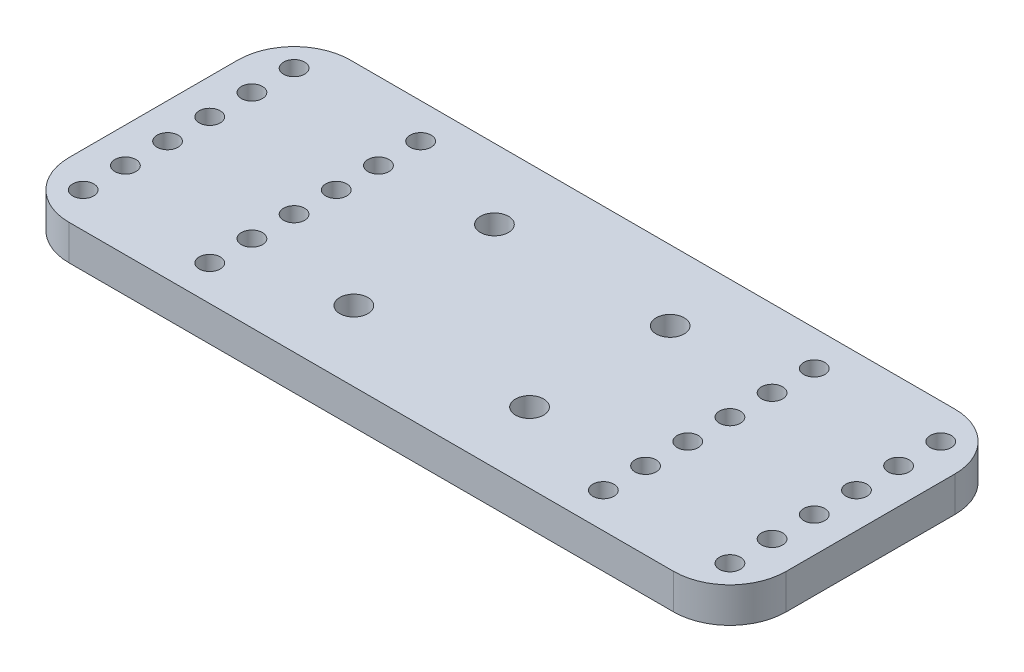
SolidWorks part; units mm, degrees
ref_plane "前视基准面" through (0, 0, 0) normal (0, 0, 1) x (1, 0, 0)
ref_plane "上视基准面" through (0, 0, 0) normal (0, 1, 0) x (1, 0, 0)
ref_plane "右视基准面" through (0, 0, 0) normal (1, 0, 0) x (0, 0, -1)
sketch "草图1" plane through (0, 0, 0) normal (0, 1, 0) x (1, 0, 0)
  line L1 (51, -20) -> (-51, -20)
  line L2 (51, -20) -> (51, 20)
  line L3 (51, 20) -> (-51, 20)
  line L4 (-51, -20) -> (-51, 20)
  line L5 (51, -20) -> (-51, 20) construction
  line L6 (51, 20) -> (-51, -20) construction
  point P0 (0, 0)
  dimension "D1" = 40
  dimension "D2" = 102
extrude "凸台-拉伸1" add sketch "草图1" along normal blind 5
sketch "草图2" plane through (0, 5, 0) normal (0, 1, 0) x (1, 0, 0)
  line L0 (0, 20) -> (0, 10.2709)
  line L1 (51, 20) -> (-51, 20) construction
  line L2 (51, 0) -> (38.1099, 0)
  line L3 (51, -20) -> (51, 20) construction
  circle A0 centre (-46, 3) radius 1.5
  circle A1 centre (-28, 3) radius 1.5
  circle A2 centre (-28, -3) radius 1.5
  circle A3 centre (-46, -3) radius 1.5
  circle A4 centre (-28, 15) radius 1.5
  circle A5 centre (-28, 9) radius 1.5
  circle A6 centre (-46, 15) radius 1.5
  circle A7 centre (-46, 9) radius 1.5
  circle A12 centre (-46, -9) radius 1.5
  circle A13 centre (-46, -15) radius 1.5
  circle A14 centre (-28, -9) radius 1.5
  circle A15 centre (-28, -15) radius 1.5
  circle A16 centre (28, -15) radius 1.5
  circle A17 centre (28, -9) radius 1.5
  circle A18 centre (46, -15) radius 1.5
  circle A19 centre (46, -9) radius 1.5
  circle A24 centre (46, 9) radius 1.5
  circle A25 centre (46, 15) radius 1.5
  circle A26 centre (28, 9) radius 1.5
  circle A27 centre (28, 15) radius 1.5
  circle A28 centre (46, -3) radius 1.5
  circle A29 centre (28, -3) radius 1.5
  circle A30 centre (28, 3) radius 1.5
  circle A31 centre (46, 3) radius 1.5
  dimension "D1" = 18
  dimension "D2" = 18
  dimension "D3" = 6
  dimension "D4" = 6
  dimension "D5" = 3
  dimension "D6" = 3
  dimension "D7" = 3
  dimension "D8" = 3
  dimension "D9" = 28
  dimension "D10" = 28
  dimension "D11" = 3
  dimension "D12" = 3
  dimension "D13" = 2
extrude "切除-拉伸1" cut sketch "草图2" against normal through all contours A6 | A7 | A0 | A12 | A3 | A13 | A15 | A14 | A2 | A1 | A5 | A4 | A16 | A17 | A29 | A30 | A26 | A27 | A18 | A19 | A31 | A24 | A25 | A28 region at (-46, 5, -3) region at (-28, 5, -3) region at (-28, 5, 3) region at (-46, 5, 3) region at (-28, 5, -15) region at (-28, 5, -9) region at (-46, 5, -15) region at (-46, 5, -9) region at (-46, 5, 9) region at (-46, 5, 15) region at (-28, 5, 9) region at (-28, 5, 15) region at (28, 5, 15) region at (28, 5, 9) region at (46, 5, 15) region at (46, 5, 9) region at (46, 5, -9) region at (46, 5, -15) region at (28, 5, -9) region at (28, 5, -15) region at (28, 5, 3) region at (28, 5, -3) region at (46, 5, -3)
sketch "草图3" plane through (0, 5, 0) normal (0, 1, 0) x (1, 0, 0)
  circle A0 centre (-12.5, 10) radius 2
  circle A1 centre (12.5, 10) radius 2
  circle A2 centre (12.5, -10) radius 2
  circle A3 centre (-12.5, -10) radius 2
  dimension "D1" = 20
  dimension "D2" = 20
  dimension "D3" = 10
  dimension "D4" = 10
  dimension "D5" = 25
  dimension "D6" = 25
  dimension "D7" = 12.5
  dimension "D8" = 4
  dimension "D9" = 4
  dimension "D10" = 4
  dimension "D11" = 4
  dimension "D12" = 12.5
extrude "切除-拉伸2" cut sketch "草图3" against normal blind 5
fillet "圆角1" radius 8 4 edges at (51, 2.5, -20) (51, 2.5, 20) (-51, 2.5, 20) (-51, 2.5, -20)
